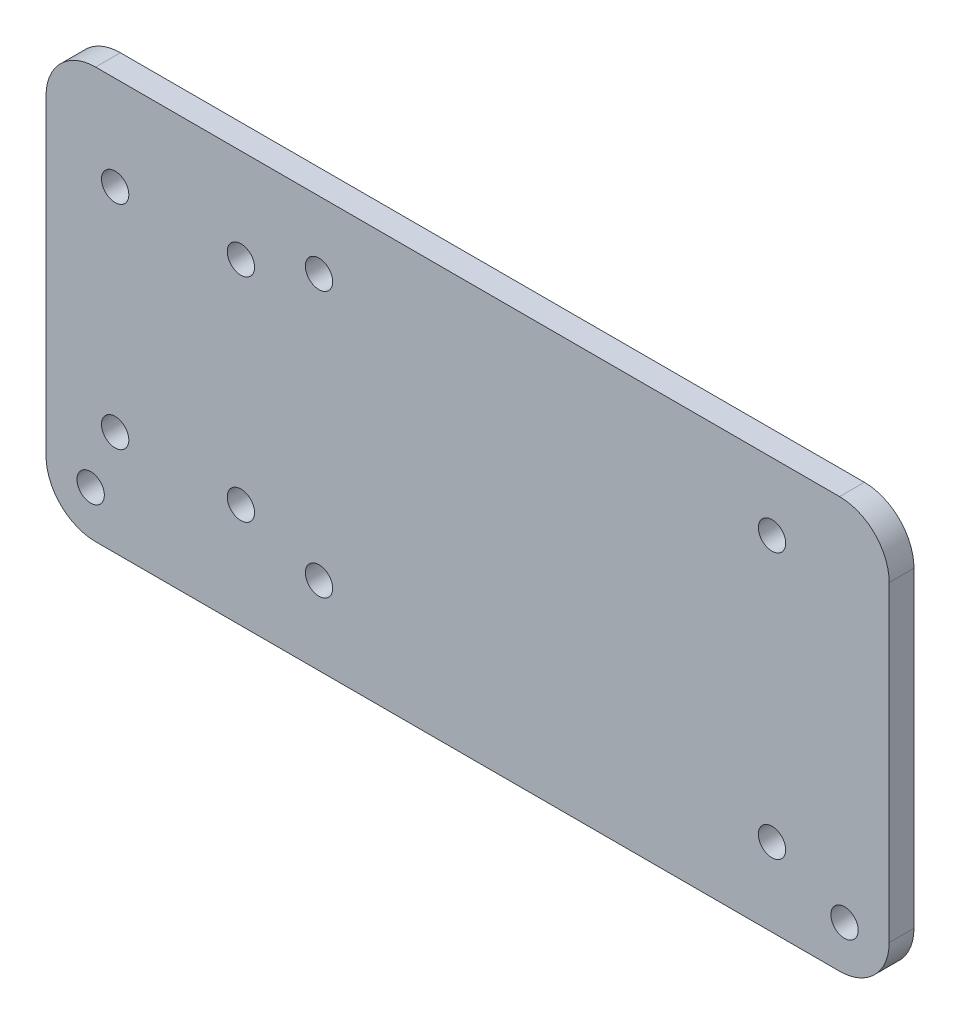
SolidWorks part; units mm, degrees
ref_plane "Front" through (0, 0, 0) normal (0, 0, 1) x (1, 0, 0)
ref_plane "Top" through (0, 0, 0) normal (0, 1, 0) x (1, 0, 0)
ref_plane "Right" through (0, 0, 0) normal (1, 0, 0) x (0, 0, -1)
sketch "Sketch1" plane through (0, 0, 0) normal (0, 0, 1) x (1, 0, 0)
  line L1 (-53.975, -43.815) -> (53.975, -43.815)
  line L2 (-53.975, -43.815) -> (-53.975, 43.815)
  line L3 (-53.975, 43.815) -> (53.975, 43.815)
  line L4 (53.975, -43.815) -> (53.975, 43.815)
  line L5 (-53.975, -43.815) -> (53.975, 43.815) construction
  line L6 (-53.975, 43.815) -> (53.975, -43.815) construction
  point P0 (0, 0)
  dimension "D1" = 107.95
  dimension "D2" = 87.63
extrude "Boss-Extrude1" add sketch "Sketch1" along normal blind 3.175
sketch "Sketch2" plane through (0, 0, 3.175) normal (0, 0, 1) x (1, 0, 0)
  line L1 (-48.26, -38.1) -> (48.26, -38.1) construction
  line L2 (-48.26, -38.1) -> (-48.26, 38.1) construction
  line L3 (-48.26, 38.1) -> (48.26, 38.1) construction
  line L4 (48.26, -38.1) -> (48.26, 38.1) construction
  line L5 (-48.26, -38.1) -> (48.26, 38.1) construction
  line L6 (-48.26, 38.1) -> (48.26, -38.1) construction
  circle A0 centre (-48.26, 38.1) radius 1.75
  circle A1 centre (48.26, 38.1) radius 1.75
  circle A2 centre (48.26, -38.1) radius 1.75
  circle A3 centre (-48.26, -38.1) radius 1.75
  point P0 (0, 0)
  dimension "D1" = 3.5
  dimension "D2" = 96.52
  dimension "D3" = 76.2
extrude "Cut-Extrude1" cut sketch "Sketch2" against normal through all
sketch "Sketch3" plane through (0, 0, 3.175) normal (0, 0, 1) x (1, 0, 0)
  line L0 (-53.975, -43.815) -> (53.975, -43.815) construction
  line L1 (-19.025, -33.815) -> (38.975, -33.815) construction
  line L2 (-19.025, -33.815) -> (-19.025, 0.185) construction
  line L3 (-19.025, 0.185) -> (38.975, 0.185) construction
  line L4 (38.975, -33.815) -> (38.975, 0.185) construction
  line L5 (-19.025, -33.815) -> (38.975, 0.185) construction
  line L6 (-19.025, 0.185) -> (38.975, -33.815) construction
  line L7 (53.975, -43.815) -> (53.975, 43.815) construction
  line L9 (-45.125, -30.415) -> (-29.025, -30.415) construction
  line L10 (-45.125, -30.415) -> (-45.125, -3.215) construction
  line L11 (-45.125, -3.215) -> (-29.025, -3.215) construction
  line L12 (-29.025, -30.415) -> (-29.025, -3.215) construction
  line L13 (-45.125, -30.415) -> (-29.025, -3.215) construction
  line L14 (-45.125, -3.215) -> (-29.025, -30.415) construction
  circle A0 centre (-29.025, -3.215) radius 1.75
  circle A1 centre (-29.025, -30.415) radius 1.75
  circle A2 centre (-45.125, -30.415) radius 1.75
  circle A3 centre (-45.125, -3.215) radius 1.75
  circle A4 centre (-19.025, -33.815) radius 1.75
  circle A5 centre (38.975, -33.815) radius 1.75
  circle A6 centre (38.975, 0.185) radius 1.75
  circle A7 centre (-19.025, 0.185) radius 1.75
  circle A8 centre (-48.26, -38.1) radius 1.75 construction
  point P0 (9.975, -16.815)
  point P9 (-37.075, -16.815)
  dimension "D1" = 34
  dimension "D2" = 58
  dimension "D3" = 10
  dimension "D4" = 15
  dimension "D5" = 27.2
  dimension "D6" = 16.1
  dimension "D7" = 10
extrude "Cut-Extrude2" cut sketch "Sketch3" against normal through all
sketch "Sketch4" plane through (0, 0, 3.175) normal (0, 0, 1) x (1, 0, 0)
  line L0 (53.975, -43.815) -> (53.975, 43.815) construction
  line L1 (-53.975, 43.815) -> (53.975, 43.815)
  line L2 (-53.975, 43.815) -> (-53.975, 8.815)
  line L3 (-53.975, 8.815) -> (53.975, 8.815)
  line L4 (53.975, 43.815) -> (53.975, 8.815)
  dimension "D1" = 35
extrude "Cut-Extrude3" cut sketch "Sketch4" against normal through all
fillet "Fillet1" radius 6.35 4 edges at (-53.975, -43.815, 1.5875) (53.975, -43.815, 1.5875) (53.975, 8.815, 1.5875) (-53.975, 8.815, 1.5875)
